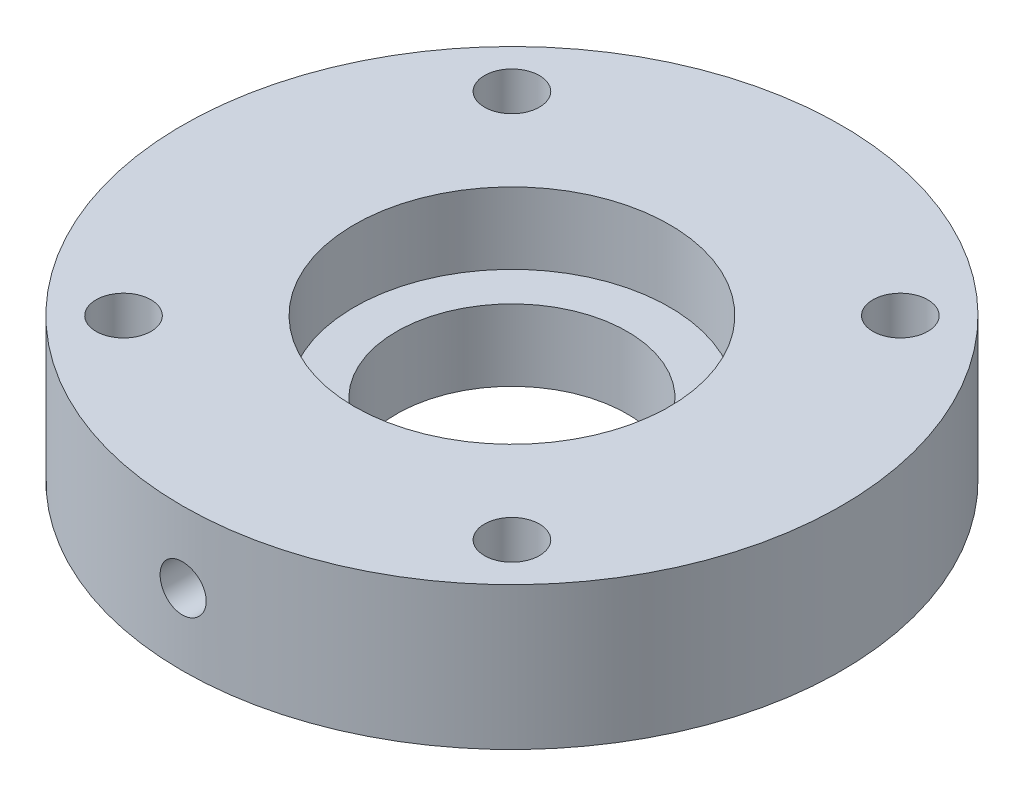
SolidWorks part; units mm, degrees
ref_plane "Front Plane" through (0, 0, 0) normal (0, 0, 1) x (1, 0, 0)
ref_plane "Top Plane" through (0, 0, 0) normal (0, 1, 0) x (1, 0, 0)
ref_plane "Right Plane" through (0, 0, 0) normal (1, 0, 0) x (0, 0, -1)
sketch "Sketch1" plane through (0, 0, 0) normal (0, 1, 0) x (1, 0, 0)
  line L0 (-17.6777, 17.6777) -> (17.6777, -17.6777) construction
  line L1 (0, 0) -> (-30, 0) construction
  line L2 (17.6777, 17.6777) -> (-17.6777, -17.6777) construction
  circle A0 centre (0, 0) radius 10.5
  circle A1 centre (0, 0) radius 14.2875 construction
  circle A2 centre (0, 0) radius 30
  circle A3 centre (0, 0) radius 25 construction
  circle A4 centre (17.6777, 17.6777) radius 2.5
  circle A5 centre (17.6777, -17.6777) radius 2.5
  circle A6 centre (-17.6777, -17.6777) radius 2.5
  circle A7 centre (-17.6777, 17.6777) radius 2.5
  dimension "D1" = 21
  dimension "D2" = 28.575
  dimension "D3" = 60
  dimension "D4" = 50
  dimension "D5" = 5
  dimension "D6" = 45
extrude "Boss-Extrude1" add sketch "Sketch1" along normal blind 6.5 and the other way blind 6.5
sketch "Sketch2" plane through (0, 0, 0) normal (0, 1, 0) x (1, 0, 0)
  circle A0 centre (0, 0) radius 14.35
  dimension "D1" = 28.7
extrude "Cut-Extrude1" cut sketch "Sketch2" along normal blind 7.9375
sketch "Sketch3" plane through (0, 0, 0) normal (0, 1, 0) x (1, 0, 0)
  circle A0 centre (17.6777, 17.6777) radius 4.5
  circle A1 centre (17.6777, -17.6777) radius 4.5
  circle A2 centre (-17.6777, -17.6777) radius 4.5
  circle A3 centre (-17.6777, 17.6777) radius 4.5
  dimension "D1" = 9
extrude "Cut-Extrude3" cut sketch "Sketch3" along normal blind 6 from surface starting at face at (-17.6777, -6.5, -15.1777)
sketch "Sketch4" plane through (0, 0, 0) normal (0, 0, 1) x (1, 0, 0)
  circle A0 centre (0, 0) radius 2.1
  dimension "D1" = 4.2
extrude "Cut-Extrude4" cut sketch "Sketch4" against normal blind 15 from offset 30
